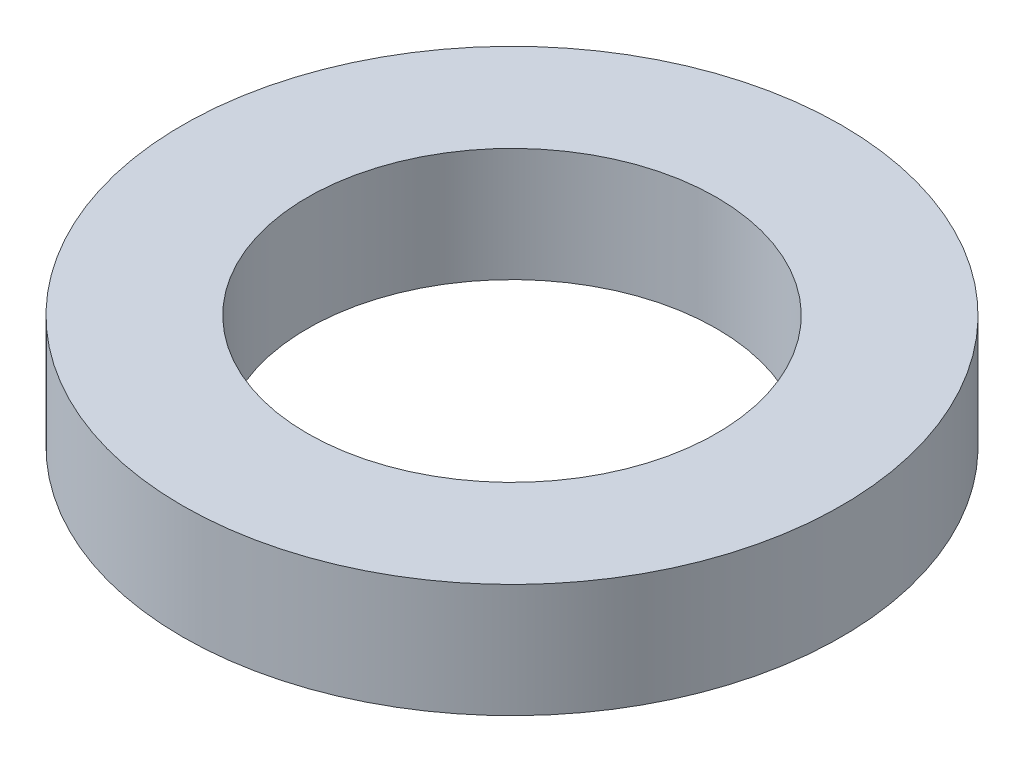
SolidWorks part; units mm, degrees
ref_plane "Front Plane" through (0, 0, 0) normal (0, 0, 1) x (1, 0, 0)
ref_plane "Top Plane" through (0, 0, 0) normal (0, 1, 0) x (1, 0, 0)
ref_plane "Right Plane" through (0, 0, 0) normal (1, 0, 0) x (0, 0, -1)
sketch "Sketch1" plane through (0, 0, 0) normal (0, 1, 0) x (1, 0, 0)
  circle A0 centre (0, 0) radius 72.5
  dimension "FLANGE_OD" = 145
extrude "Boss-Extrude1" add sketch "Sketch1" along normal blind 25
sketch "Sketch2" plane through (0, 0, 0) normal (0, 1, 0) x (1, 0, 0)
  circle A0 centre (0, 0) radius 45
  dimension "BORE_D" = 90
extrude "Cut-Extrude1" cut sketch "Sketch2" along normal through all
sketch "Sketch3" plane through (0, 25, 0) normal (0, 1, 0) x (1, 0, 0)
  circle A0 centre (0, 0) radius 26.8607 construction
  circle A1 centre (-26.8607, 0) radius 2.8817
  dimension "BOLT_D" = 5.7633
  dimension "BOLT_PCD" = 53.7215
extrude "Cut-Extrude2" cut sketch "Sketch3" against normal blind 20.3178 rebuild error yes
pattern_circular "CirPattern1" count 3 over 360 rebuild error yes
